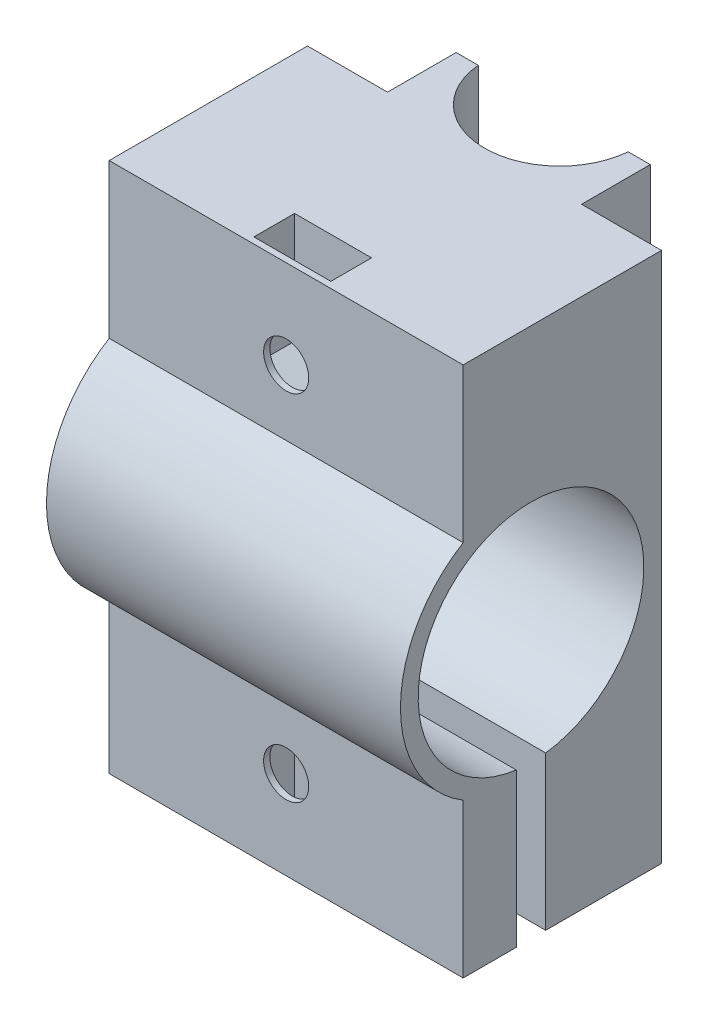
SolidWorks part; units mm, degrees
ref_plane "Front" through (0, 0, 0) normal (0, 0, 1) x (1, 0, 0)
ref_plane "Top" through (0, 0, 0) normal (0, 1, 0) x (1, 0, 0)
ref_plane "Right" through (0, 0, 0) normal (1, 0, 0) x (0, 0, -1)
ref_axis "Center Axis" through (0, 0, -88.99) along (0, 0, 1)
sketch "Sketch2" plane through (0, 0, 0) normal (1, 0, 0) x (0, 0, -1)
  line L0 (-18.306, -16.054) -> (-14.079, -16.054) construction
  line L1 (-16.1925, -16.054) -> (-16.1925, 0) construction
  line L2 (-18.306, -16.054) -> (-18.306, -38.1)
  line L3 (-18.306, -38.1) -> (-25.926, -38.1)
  line L4 (-25.926, -38.1) -> (-25.926, -16.0051)
  line L5 (-14.079, -16.054) -> (-14.079, -38.1)
  line L6 (-14.079, -38.1) -> (2.54, -38.1)
  line L7 (2.54, -38.1) -> (2.54, 38.1)
  line L9 (-25.926, 16.0051) -> (-25.926, 38.1)
  line L10 (-25.926, 38.1) -> (2.54, 38.1)
  line L11 (-16.1925, 16.1925) -> (-16.1925, 38.1) construction
  arc A0 (-14.079, -16.054) -> (-18.306, -16.054) centre (-16.1925, 0) ccw
  arc A1 (-25.926, -16.0051) -> (-25.926, 16.0051) centre (-16.1925, 0) cw
  dimension "D1" = 32.385
  dimension "D4" = 2.54
  dimension "D2" = 15
  dimension "D3" = 2.54
  dimension "D5" = 76.2
  dimension "D6" = 7.62
  dimension "D7" = 4.2271
sketch "Sketch1" plane through (0, 0, 0) normal (0, 1, 0) x (1, 0, 0)
  line L2 (-13.9289, 0) -> (13.9289, 0)
  line L4 (0, 2.54) -> (0, 0) construction
  line L5 (10.7539, 12.3942) -> (13.9289, 12.3942)
  line L6 (13.9289, 12.3942) -> (13.9289, 0)
  line L7 (-10.7539, 12.3942) -> (-13.9289, 12.3942)
  line L8 (-13.9289, 12.3942) -> (-13.9289, 0)
  arc A1 (-10.7539, 12.3942) -> (10.7539, 12.3942) centre (0, 13.335) ccw
  dimension "D1" = 21.59
  dimension "D2" = 2.54
  dimension "D4" = 190
  dimension "D3" = 3.175
extrude "Boss-Extrude1" add sketch "Sketch1" along normal mid plane 76.2
extrude "Boss-Extrude2" add sketch "Sketch2" along normal mid plane 50.8
ref_plane "Plane1" through (0, 0, 22.116) normal (0, 0, 1) x (1, 0, 0)
sketch "Sketch3" plane through (0, 0, 22.116) normal (0, 0, 1) x (1, 0, 0)
  line L1 (5.5245, -28.5896) -> (5.5245, -22.2104)
  line L2 (5.5245, -22.2104) -> (0, -19.0209)
  line L3 (0, -19.0209) -> (-5.5245, -22.2104)
  line L4 (-5.5245, -22.2104) -> (-5.5245, -28.5896)
  line L5 (-5.5245, -28.5896) -> (0, -31.7791) construction
  line L6 (0, -31.7791) -> (5.5245, -28.5896) construction
  line L7 (-5.5245, -28.5896) -> (-5.5245, -38.1)
  line L8 (25.4, -38.1) -> (-25.4, -38.1) construction
  line L9 (-5.5245, -38.1) -> (5.5245, -38.1)
  line L10 (5.5245, -38.1) -> (5.5245, -28.5896)
  line L11 (25.4, -16.0051) -> (-25.4, -16.0051) construction
  circle A0 centre (0, -25.4) radius 5.5245 construction
  dimension "D1" = 3.0157
  dimension "D2" = 11.049
  dimension "D3" = 25.4
extrude "Cut-Extrude1" cut sketch "Sketch3" against normal mid plane 5.842
sketch "Sketch5" plane through (0, 0, 0) normal (0, 0, 1) x (1, 0, 0)
  circle A0 centre (0, -25.4) radius 3.2385
  dimension "D1" = 6.477
extrude "Cut-Extrude3" cut sketch "Sketch5" against normal through all both and the other way through all
mirror "Mirror1" about plane through (0, 0, 0) normal (0, 1, 0) of "Cut-Extrude3", "Cut-Extrude1"
